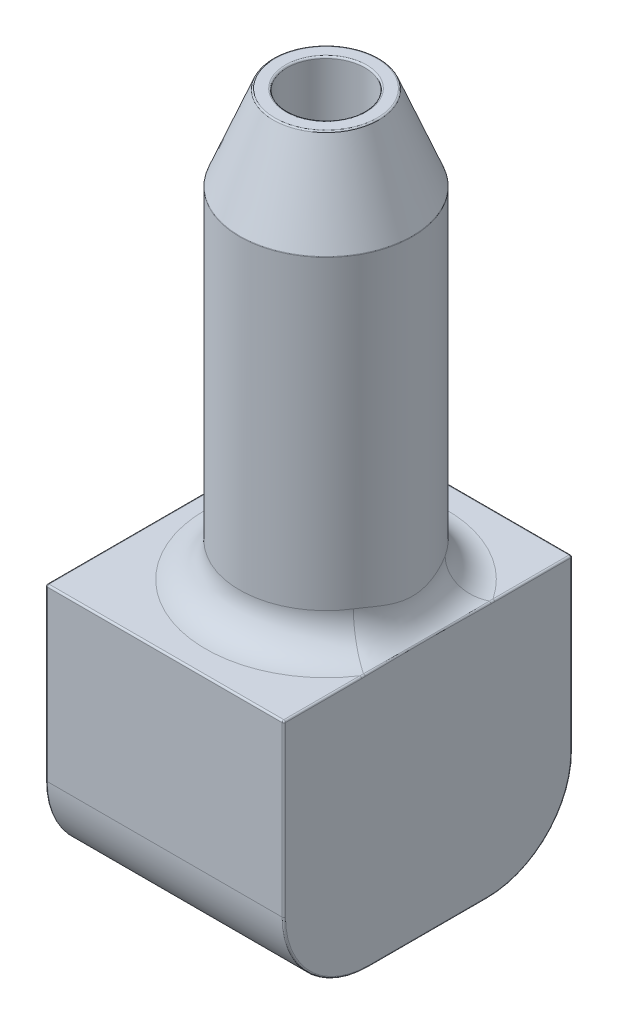
SolidWorks part; units mm, degrees
ref_plane "Front Plane" through (0, 0, 0) normal (0, 0, 1) x (1, 0, 0)
ref_plane "Top Plane" through (0, 0, 0) normal (0, 1, 0) x (1, 0, 0)
ref_plane "Right Plane" through (0, 0, 0) normal (1, 0, 0) x (0, 0, -1)
sketch "Sketch2" plane through (0, 0, 0) normal (0, 1, 0) x (1, 0, 0)
  line L1 (8, 8.4815) -> (-8, 8.4815)
  line L2 (8, 8.4815) -> (8, -8.4815)
  line L3 (8, -8.4815) -> (-8, -8.4815)
  line L4 (-8, 8.4815) -> (-8, -8.4815)
  line L5 (8, 8.4815) -> (-8, -8.4815) construction
  line L6 (8, -8.4815) -> (-8, 8.4815) construction
  point P0 (0, 0)
  dimension "D1" = 16.963
  dimension "D2" = 16
extrude "Boss-Extrude1" add sketch "Sketch2" along normal blind 15
sketch "Sketch3" plane through (0, 15, 0) normal (0, 1, 0) x (1, 0, 0)
  circle A0 centre (0, 0) radius 5.08
  circle A1 centre (0, 0) radius 2.285
  dimension "D1" = 10.16
  dimension "D2" = 4.57
extrude "Boss-Extrude2" add sketch "Sketch3" along normal blind 25
sketch "Sketch4" plane through (8, 0, 0) normal (1, 0, 0) x (0, 0, -1)
  line L14 (8.4815, 15) -> (-8.4815, 15)
  line L15 (-8.4815, 0) -> (8.4815, 0)
  line L16 (-8.4815, 15) -> (-8.4815, 0)
  line L17 (8.4815, 0) -> (8.4815, 15)
  line L18 (8.4815, 15) -> (-8.4815, 15)
  line L19 (-8.4815, 0) -> (8.4815, 0)
  line L20 (-8.4815, 15) -> (-8.4815, 0)
  line L21 (8.4815, 0) -> (8.4815, 15)
  dimension "D1" = 0
extrude "Cut-Extrude1" cut sketch "Sketch4" against normal blind 2
chamfer "Chamfer1" distance 5 distance2 2 1 edges at (0, 40, 5.08) first distance on face at (0, 40, 5.08)
fillet "Fillet1" radius 5 2 edges at (-1, 0, 8.4815) (-1, 0, -8.4815)
fillet "Fillet2" radius 2 1 edges at (0, 15, -5.08)
sketch "Sketch5" plane through (0, 15, 0) normal (0, 1, 0) x (1, 0, 0)
  circle A2 centre (0, 0) radius 2.285
  circle A3 centre (0, 0) radius 2.285
  dimension "D1" = 0
extrude "Cut-Extrude2" cut sketch "Sketch5" against normal through all both and the other way through all
ref_axis "Axis1" through (0, 40, 0) along (0, -1, 0)
fillet "Fillet3" radius 0.1 20 edges at (-1, 15, -8.4815) (0, 0, 2.285) (0, 40, 3.08) (0, 35, 5.08) (-1, 15, 8.4815) (6, 15, 6.12) (6, 15, 0) (6, 15, -6.12) (6, 10, -8.4815) (6, 1.4645, -7.017) (6, 0, 0) (6, 1.4645, 7.017) (6, 10, 8.4815) (-8, 1.4645, -7.017) (-8, 10, -8.4815) (-8, 15, 0) (-8, 10, 8.4815) (-8, 1.4645, 7.017) (-8, 0, 0) (0, 40, 2.285)
